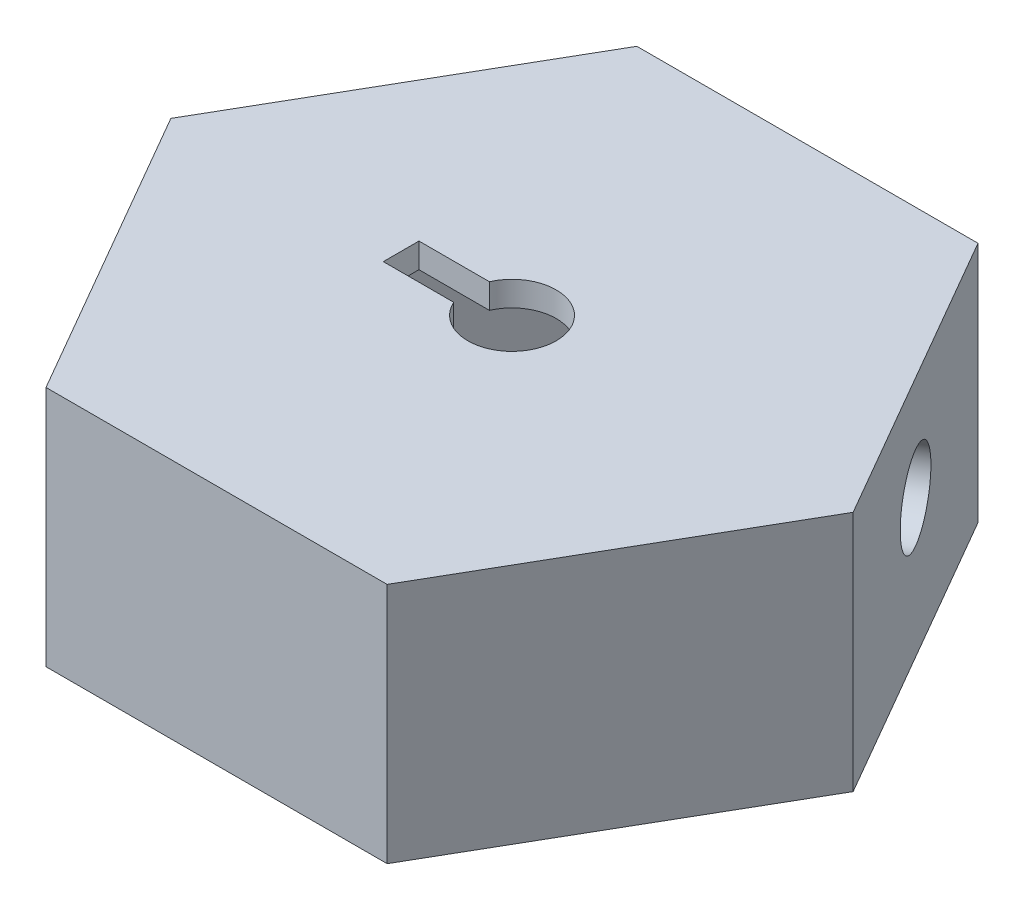
SolidWorks part; units mm, degrees
ref_plane "Front Plane" through (0, 0, 0) normal (0, 0, 1) x (1, 0, 0)
ref_plane "Top Plane" through (0, 0, 0) normal (0, 1, 0) x (1, 0, 0)
ref_plane "Right Plane" through (0, 0, 0) normal (1, 0, 0) x (0, 0, -1)
sketch "Sketch1" plane through (0, 0, 0) normal (0, 1, 0) x (1, 0, 0)
  line L1 (27.94, 0) -> (13.97, 24.1967)
  line L2 (13.97, 24.1967) -> (-13.97, 24.1967)
  line L3 (-13.97, 24.1967) -> (-27.94, 0)
  line L4 (-27.94, 0) -> (-13.97, -24.1967)
  line L5 (-13.97, -24.1967) -> (13.97, -24.1967)
  line L6 (13.97, -24.1967) -> (27.94, 0)
  line L7 (-9.0805, 1.4605) -> (-3.3118, 1.4605)
  line L8 (-9.0805, 1.4605) -> (-9.0805, -1.4605)
  line L9 (-9.0805, -1.4605) -> (-3.3118, -1.4605)
  circle A0 centre (0, 0) radius 3.6195
  circle A1 centre (0, 0) radius 24.1967 construction
  point P14 (-9.0805, 0)
  point P15 (-17.1402, 18.745)
  point P16 (-12.2984, 22.2241)
  dimension "D1" = 7.239
  dimension "D2" = 2.921
  dimension "D3" = 5.461
  dimension "D4" = 55.88
extrude "Boss-Extrude1" add sketch "Sketch1" along normal blind 2.032 contours L5 L6 L1 L2 L3 L4 A0 L9 L8 L7 region at (20.3148, 0, 11.7288)
sketch "Sketch2" plane through (0, 0, 0) normal (0, -1, 0) x (1, 0, 0)
  line L0 (-13.97, 24.1967) -> (13.97, 24.1967) construction
  line L1 (13.97, 24.1967) -> (-13.97, 24.1967)
  line L2 (-13.97, 24.1967) -> (-27.94, 0)
  line L3 (-27.94, 0) -> (-13.97, -24.1967)
  line L4 (-13.97, -24.1967) -> (13.97, -24.1967)
  line L5 (13.97, -24.1967) -> (27.94, 0)
  line L6 (27.94, 0) -> (13.97, 24.1967)
  line L7 (12.7968, 22.1647) -> (-12.7968, 22.1647)
  line L8 (-12.7968, 22.1647) -> (-25.5936, 0)
  line L9 (-25.5936, 0) -> (-12.7968, -22.1647)
  line L10 (-12.7968, -22.1647) -> (12.7968, -22.1647)
  line L11 (12.7968, -22.1647) -> (25.5936, 0)
  line L12 (25.5936, 0) -> (12.7968, 22.1647)
  circle A0 centre (0, 0) radius 24.1967 construction
  point P1 (11.3217, 16.7942)
  dimension "D1" = 2.032
extrude "Boss-Extrude2" add sketch "Sketch2" along normal blind 17.78
sketch "Sketch4" plane through (20.955, 0, -12.0984) normal (0.866, 0, -0.5) x (-0.5, 0, -0.866)
  line L0 (13.97, -17.78) -> (-13.97, -17.78) construction
  line L6 (-13.97, 2.032) -> (13.97, 2.032) construction
  circle A0 centre (0, -6.477) radius 3.429
  point P0 (0, 0)
  point P3 (0, -17.78)
  dimension "D1" = 5.08
  dimension "D2" = 6.858
extrude "Cut-Extrude1" cut sketch "Sketch4" against normal up to next
ref_axis "Axis1" through (0, 2.7686, 0) along (0, -1, 0)
pattern_circular "CirPattern1" count 3 every 60 about axis through (0, 2.7686, 0) along (0, -1, 0) of "Cut-Extrude1" reverse direction yes
